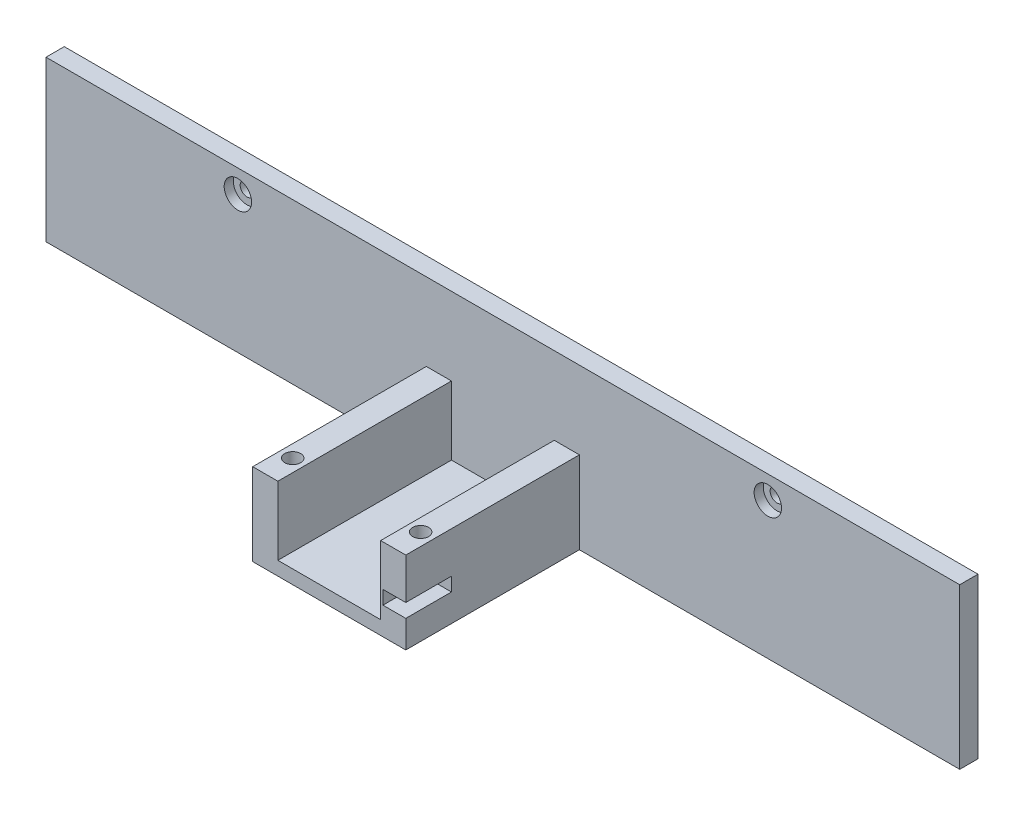
SolidWorks part; units mm, degrees
ref_plane "Front Plane" through (0, 0, 0) normal (0, 0, 1) x (1, 0, 0)
ref_plane "Top Plane" through (0, 0, 0) normal (0, 1, 0) x (1, 0, 0)
ref_plane "Right Plane" through (0, 0, 0) normal (1, 0, 0) x (0, 0, -1)
sketch "Sketch1" plane through (0, 0, 0) normal (0, 0, 1) x (1, 0, 0)
  line L0 (100, 40) -> (100, 0) construction
  line L1 (0, 0) -> (200, 0)
  line L2 (0, 0) -> (0, 40)
  line L3 (0, 40) -> (200, 40)
  line L4 (200, 0) -> (200, 40)
  line L5 (0, 35) -> (200, 35)
  line L6 (9, 35) -> (9, 40)
  line L7 (191, 35) -> (191, 40)
  line L9 (42, 0) -> (158, 0)
  line L10 (42, 0) -> (42, -5)
  line L11 (42, -5) -> (158, -5)
  line L12 (158, 0) -> (158, -5)
  circle A0 centre (158, 30) radius 1.5
  circle A1 centre (158, 30) radius 3
  circle A2 centre (42, 30) radius 3
  circle A3 centre (42, 30) radius 1.5
  dimension "D3" = 3
  dimension "D4" = 6
  dimension "D1" = 35
  dimension "D2" = 200
  dimension "D5" = 10
  dimension "D6" = 42
  dimension "D7" = 5
  dimension "D8" = 9
  dimension "D9" = 5
extrude "Body" add sketch "Sketch1" along normal blind 4 contours L0 L3 L2 L5 A2 | L3 L0 L5 L4 A1 region at (149.9348, 17.3982, 0) region at (50.0652, 17.3982, 0)
extrude "Screw Inserts" add sketch "Sketch1<3>" along normal blind 2 contours A2 A3 | A1 A0 region at (155.0849, 30, 0) region at (39.0849, 30, 0)
sketch "Sketch1<3>" plane through (0, 0, 0) normal (0, 0, 1) x (1, 0, 0) same geometry as "Sketch1"
sketch "Sketch2" plane through (0, 0, 4) normal (0, 0, 1) x (1, 0, 0)
  line L0 (100, 35) -> (100, 0) construction
  line L1 (0, 35) -> (200, 35) construction
  line L3 (100, 18) -> (100, 0) construction
  line L4 (83.25, 18) -> (116.75, 18)
  line L5 (83.25, 18) -> (83.25, 0)
  line L6 (83.25, 0) -> (116.75, 0)
  line L7 (116.75, 18) -> (116.75, 0)
  line L8 (100, 18) -> (100, 3) construction
  line L9 (88.75, 18) -> (111.25, 18)
  line L10 (88.75, 18) -> (88.75, 3)
  line L11 (88.75, 3) -> (111.25, 3)
  line L12 (111.25, 18) -> (111.25, 3)
  line L13 (83.25, 3) -> (116.75, 3)
  line L16 (0, 0) -> (200, 0) construction
  dimension "D1" = 3
  dimension "D2" = 33.5
  dimension "D3" = 15
  dimension "D4" = 22.5
  dimension "D5" = 15
extrude "Servo Insert" add sketch "Sketch2" along normal blind 38 contours L5 L13 L10 L4 | L13 L5 L7 L11 | L12 L13 L7 L4 region at (86, 10.5, 4) region at (100, 1.5, 4) region at (114, 10.5, 4)
sketch "Sketch3" plane through (0, 0, 42) normal (0, 0, 1) x (1, 0, 0)
  line L0 (116.75, 18) -> (116.75, 0) construction
  line L1 (111.75, 6) -> (116.75, 6)
  line L2 (111.75, 6) -> (111.75, 9)
  line L3 (111.75, 9) -> (116.75, 9)
  line L4 (116.75, 6) -> (116.75, 9)
  line L6 (83.25, 0) -> (116.75, 0) construction
  dimension "D1" = 3
  dimension "D2" = 5
  dimension "D3" = 6
extrude "Wire Channel" cut sketch "Sketch3" against normal blind 10
sketch "Sketch4" plane through (0, 18, 0) normal (0, 1, 0) x (1, 0, 0)
  line L0 (111.25, -4) -> (88.75, -4) construction
  line L1 (100, -4) -> (100, -43.0391) construction
  line L2 (86, -42) -> (86, -30.5842) construction
  line L3 (83.25, -42) -> (88.75, -42) construction
  circle A0 centre (86, -36) radius 1.75
  circle A1 centre (114, -36) radius 1.75
  point P12 (0, 0)
  dimension "D1" = 3.5
  dimension "D2" = 6
extrude "M2x4x3.5" cut sketch "Sketch4" against normal blind 6
